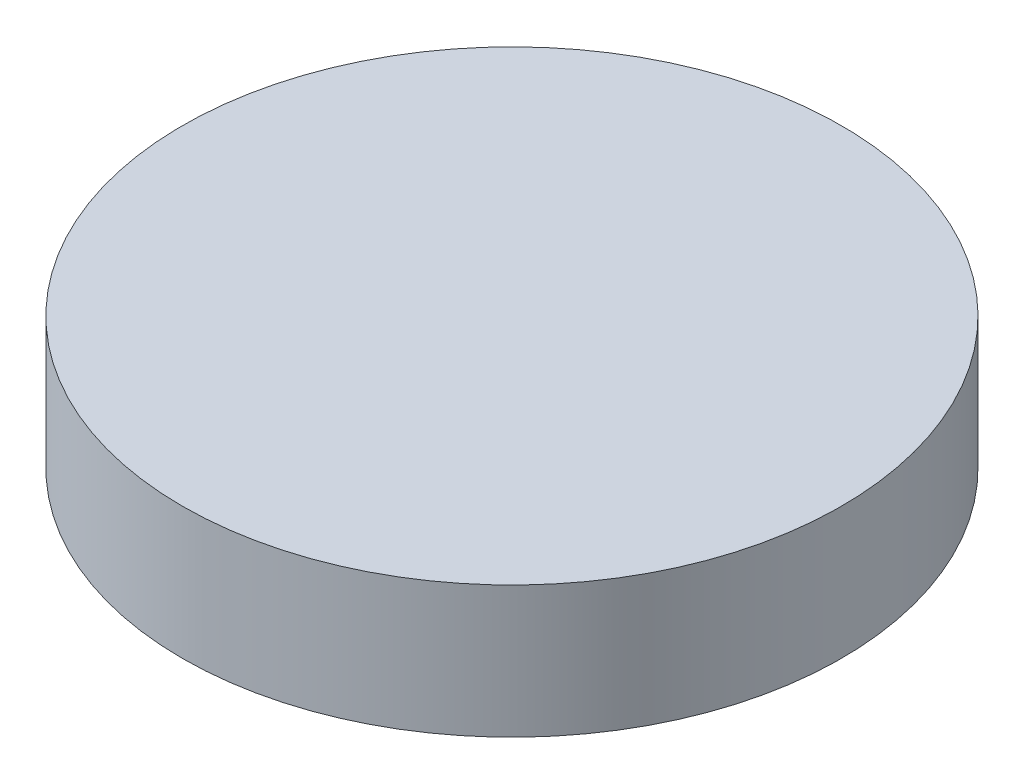
SolidWorks part; units mm, degrees
ref_plane "Front Plane" through (0, 0, 0) normal (0, 0, 1) x (1, 0, 0)
ref_plane "Top Plane" through (0, 0, 0) normal (0, 1, 0) x (1, 0, 0)
ref_plane "Right Plane" through (0, 0, 0) normal (1, 0, 0) x (0, 0, -1)
sketch "Sketch1" plane through (0, 0, 0) normal (0, 1, 0) x (1, 0, 0)
  circle A0 centre (0, 0) radius 15
  dimension "D1" = 30
extrude "Boss-Extrude1" add sketch "Sketch1" along normal blind 3 and the other way blind 3
